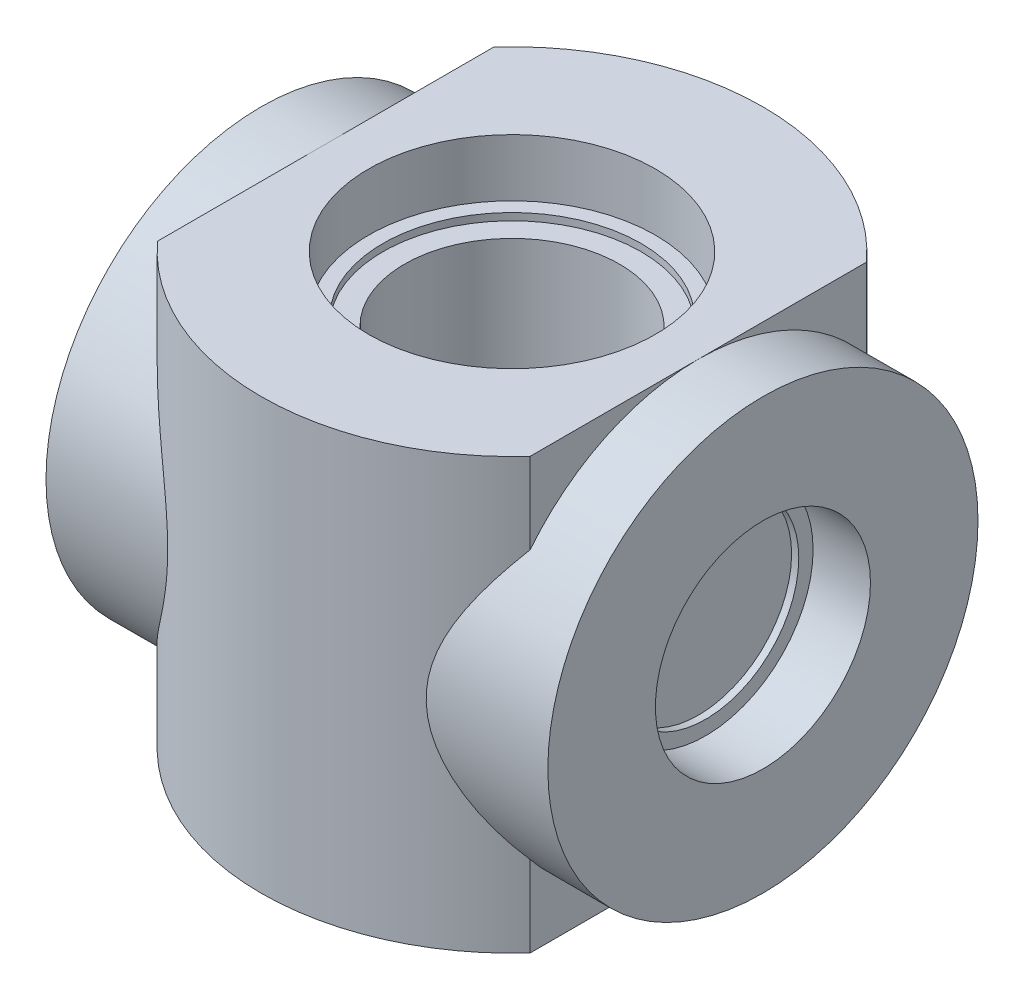
SolidWorks part; units mm, degrees
ref_plane "Front Plane" through (0, 0, 0) normal (0, 0, 1) x (1, 0, 0)
ref_plane "Top Plane" through (0, 0, 0) normal (0, 1, 0) x (1, 0, 0)
ref_plane "Right Plane" through (0, 0, 0) normal (1, 0, 0) x (0, 0, -1)
sketch "Sketch3" plane through (0, 0, 0) normal (0, 1, 0) x (1, 0, 0)
  line L0 (0, 0) -> (-13, 0) construction
  line L1 (-13, 0) -> (-13, 6.5)
  line L2 (-13.5, 7.5) -> (-17.5, 7.5)
  line L3 (-17.5, 7.5) -> (-17.5, 15)
  line L4 (-17.5, 15) -> (0, 15)
  line L5 (0, 15) -> (0, 0)
  line L6 (-13.5, 7.5) -> (-13.5, 6.5)
  line L7 (-13.5, 6.5) -> (-13, 6.5)
  line L8 (0, 0) -> (-13, 0)
  line L9 (-13, 0) -> (-23.8412, 0) construction
  dimension "D1" = 4.5
  dimension "D2" = 0.5
  dimension "D3" = 1
  dimension "D4" = 15
  dimension "D5" = 17.5
  dimension "D6" = 30
revolve "Revolve1" add sketch "Sketch3" angle 360 about L0 region at (-7.8029, 0, -8.051)
mirror "Mirror1" about plane through (0, 0, 0) normal (1, 0, 0) of "Revolve1"
sketch "Sketch6" plane through (0, 0, 0) normal (0, 1, 0) x (1, 0, 0)
  line L0 (-12.9936, 11.7225) -> (-12.9936, -11.7225)
  line L1 (12.9936, 11.7225) -> (12.9936, -11.7225)
  line L2 (-17.4936, 0.4737) -> (-17.4936, 3.9653) construction
  circle A0 centre (0, 0) radius 17.5
  dimension "D1" = 4.5
  dimension "D2" = 35
extrude "Boss-Extrude1" add sketch "Sketch6" against normal mid plane 30 contours L1 A0 L0 region at (0, 0, 0)
sketch "Sketch8" plane through (0, 0, 0) normal (0, 0, 1) x (1, 0, 0)
  line L0 (0, 0) -> (0, -16.9734) construction
  line L1 (0, -15) -> (10, -15)
  line L2 (-12.9936, -15) -> (12.9936, -15) construction
  line L3 (10, -15) -> (10, -11)
  line L4 (10, -11) -> (9, -11)
  line L5 (9, -11) -> (9, -10.5)
  line L6 (9, -10.5) -> (7.5, -10.5)
  line L7 (7.5, -10.5) -> (7.5, 10.5)
  line L9 (0, 0) -> (7.5, 0) construction
  line L10 (0, 15) -> (10, 15)
  line L11 (10, 15) -> (10, 11)
  line L12 (10, 11) -> (9, 11)
  line L13 (9, 11) -> (9, 10.5)
  line L14 (9, 10.5) -> (7.5, 10.5)
  line L15 (0, 15) -> (0, -15)
  dimension "D1" = 20
  dimension "D2" = 4
  dimension "D3" = 18
  dimension "D4" = 0.5
  dimension "D5" = 15
revolve "Cut-Revolve1" cut sketch "Sketch8" angle 360 about L15
